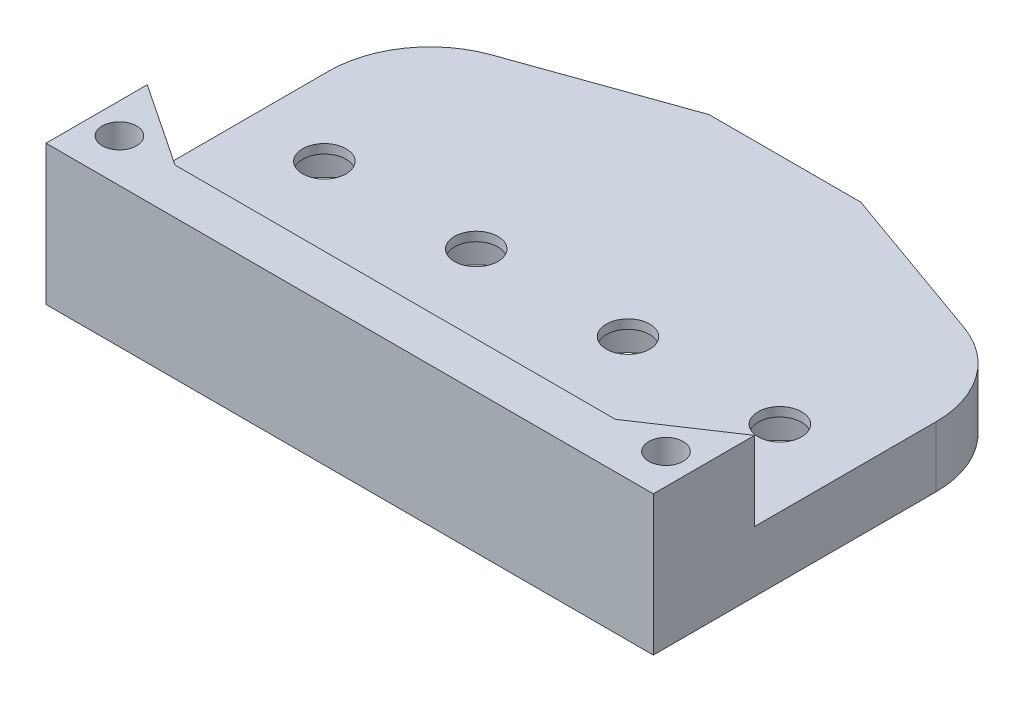
SolidWorks part; units mm, degrees
ref_plane "Front Plane" through (0, 0, 0) normal (0, 0, 1) x (1, 0, 0)
ref_plane "Top Plane" through (0, 0, 0) normal (0, 1, 0) x (1, 0, 0)
ref_plane "Right Plane" through (0, 0, 0) normal (1, 0, 0) x (0, 0, -1)
sketch "Sketch2" plane through (0, 0, 0) normal (0, 1, 0) x (1, 0, 0)
  line L0 (0, 0) -> (0, 35)
  line L1 (0, 35) -> (22.5, 43)
  line L2 (22.5, 43) -> (37.5, 43)
  line L3 (37.5, 43) -> (60, 35)
  line L4 (60, 35) -> (60, 0)
  line L5 (60, 0) -> (0, 0)
  line L6 (22.5, 20) -> (37.5, 20) construction
  line L7 (30, 43) -> (30, 0) construction
  circle A0 centre (7.5, 20) radius 2.15
  circle A1 centre (22.5, 20) radius 2.15
  circle A2 centre (37.5, 20) radius 2.15
  circle A3 centre (52.5, 20) radius 2.15
  point P17 (30, 20)
  dimension "D5" = 4.3
  dimension "D7" = 15
  dimension "D8" = 15
  dimension "D9" = 15
  dimension "D6" = 20
  dimension "D1" = 60
  dimension "D2" = 35
  dimension "D3" = 15
  dimension "D4" = 8
extrude "Boss-Extrude1" add sketch "Sketch2" along normal blind 6
sketch "Sketch3" plane through (0, 6, 0) normal (0, 1, 0) x (1, 0, 0)
  line L0 (0, 0) -> (0, 10)
  line L1 (0, 35) -> (0, 0) construction
  line L2 (0, 10) -> (15, 0)
  line L3 (0, 0) -> (60, 0) construction
  line L4 (15, 0) -> (0, 0)
  line L5 (60, 0) -> (60, 10)
  line L6 (60, 0) -> (60, 35) construction
  line L7 (60, 10) -> (45, 0)
  line L8 (45, 0) -> (60, 0)
  line L9 (51.75, 4.5) -> (8.25, 4.5)
  line M8 (0, 0) -> (60, 0)
  line M9 (60, 0) -> (60, 35)
  line M13 (0, 35) -> (0, 0)
  dimension "D1" = 15
  dimension "D2" = 10
  dimension "D3" = 4.5
extrude "Boss-Extrude2" add sketch "Sketch3" along normal blind 7.8 contours L2 M13 M8 | L7 L9 L2 M8 | L7 M9 M8 region at (5, 6, -3.3333) region at (30, 6, -2.3878) region at (55, 6, -3.3333)
sketch "Sketch4" plane through (0, 13.8, 0) normal (0, 1, 0) x (1, 0, 0)
  line L0 (0, 0) -> (60, 0) construction
  line L1 (0, 10) -> (0, 0) construction
  line L2 (60, 0) -> (60, 10) construction
  circle A0 centre (3, 4.25) radius 1.7
  circle A1 centre (57, 4.25) radius 1.7
  dimension "D1" = 3.4
  dimension "D2" = 4.25
  dimension "D3" = 3
  dimension "D4" = 3
extrude "Cut-Extrude1" cut sketch "Sketch4" against normal through all
sketch "Sketch5" plane through (0, 0, 0) normal (0, 1, 0) x (1, 0, 0)
  circle A0 centre (7.5, 20) radius 6.55
  circle A1 centre (22.5, 20) radius 6.55
  circle A2 centre (37.5, 20) radius 6.55
  circle A3 centre (52.5, 20) radius 6.55
  dimension "D1" = 13.1
extrude "Cut-Extrude2" cut sketch "Sketch5" along normal blind 5.1
fillet "Fillet1" radius 10 2 edges at (0, 3, -35) (60, 3, -35)
